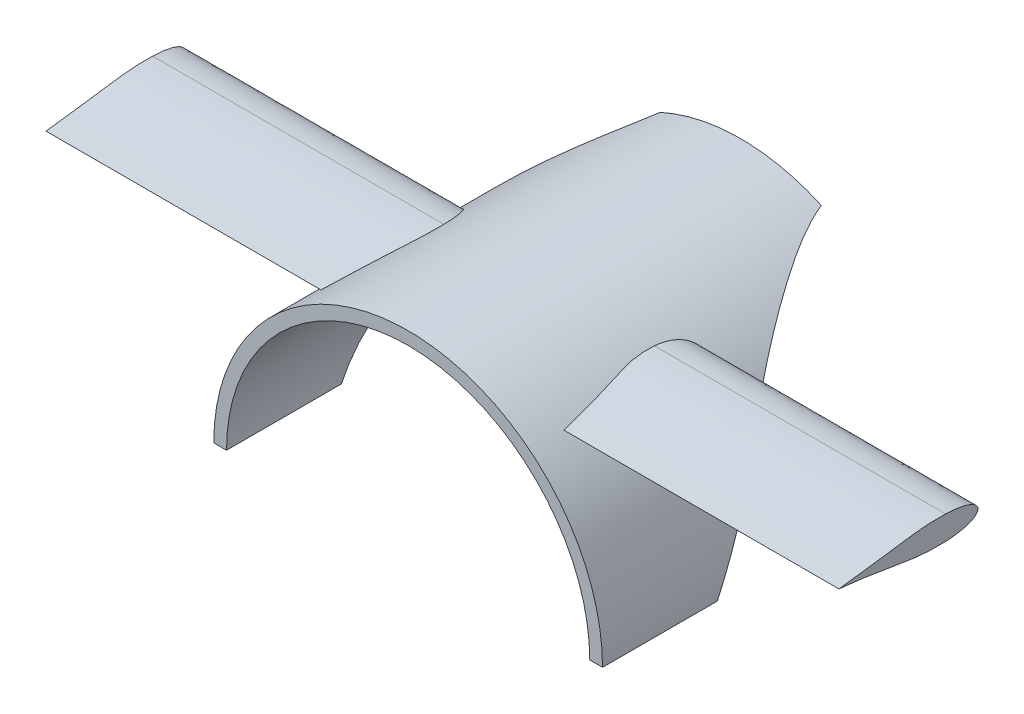
SolidWorks part; units mm, degrees
material "ABS"
ref_plane "Front Plane" through (0, 0, 0) normal (0, 0, 1) x (1, 0, 0)
ref_plane "Top Plane" through (0, 0, 0) normal (0, 1, 0) x (1, 0, 0)
ref_plane "Right Plane" through (0, 0, 0) normal (1, 0, 0) x (0, 0, -1)
sketch "Sketch4" plane through (0, 0, 0) normal (0, 0, 1) x (1, 0, 0)
  line L0 (-15.2, 0) -> (-14.2, 0)
  line L1 (14.2, 0) -> (15.2, 0)
  arc A0 (14.2, 0) -> (-14.2, 0) centre (0, 0) ccw
  arc A1 (15.2, 0) -> (-15.2, 0) centre (0, 0) ccw
extrude "RearWingBase" add sketch "Sketch4" along normal blind 26
sketch "Sketch6" plane through (0, 0, 0) normal (1, 0, 0) x (0, 0, -1)
  line L0 (-23.9267, -5.7669) -> (-19.0952, -5.7669)
  line L5 (0.0027, 13.8296) -> (0.0027, 15.1978)
  line L6 (0.0027, 15.1978) -> (5.4162, 15.1978)
  line L7 (5.4162, 15.1978) -> (5.4162, -5.7669)
  line L8 (5.4162, -5.7669) -> (-19.0952, -5.7669)
  line L9 (0, 0) -> (0, 15.2) construction
  line L17 (0, 0) -> (0, 15.2)
  spline S0 degree 3 poles (-19.0952, -5.7669) (-17.6678, -0.2793) (-14.7184, 4.4737) (-9.1615, 11.1389) (-3.6959, 13.3156) (0.0027, 13.8296) knots 0 0 0 0 0.423901 0.523901 1 1 1 1
extrude "Clearence" cut sketch "Sketch6" against normal blind 26 and the other way blind 26 contours S0 L8 L7 L6 L5 region at (0, 2.9456, 4.4966)
sketch "Sketch7" plane through (0, 0, 0) normal (1, 0, 0) x (0, 0, -1)
  spline S0 degree 3 poles (-23.3162, 11.8671) (-21.7171, 12.0552) (-17.7096, 12.6342) (-16.4962, 12.8095) (-14.9841, 12.779) knots 0 0 0 0 0.45012 1 1 1 1
  spline S1 degree 3 poles (-23.3162, 11.8671) (-19.3567, 11.5064) (-17.9656, 10.8216) (-14.9687, 10.9074) knots 0 0 0 0 1 1 1 1
  spline S2 degree 3 poles (-14.9841, 12.779) (-11.6264, 12.6689) (-11.5731, 11.0813) (-14.9687, 10.9074) knots 0 0 0 0 1 1 1 1
extrude "RearWing" add sketch "Sketch7" along normal blind 31 and the other way blind 31 contours S2 S1 S0
sketch "Sketch10" plane through (0, 0, 26) normal (0, 0, 1) x (1, 0, 0)
  circle A0 centre (0, 0) radius 14.2
extrude "Clearence2" cut sketch "Sketch10" against normal blind 26
